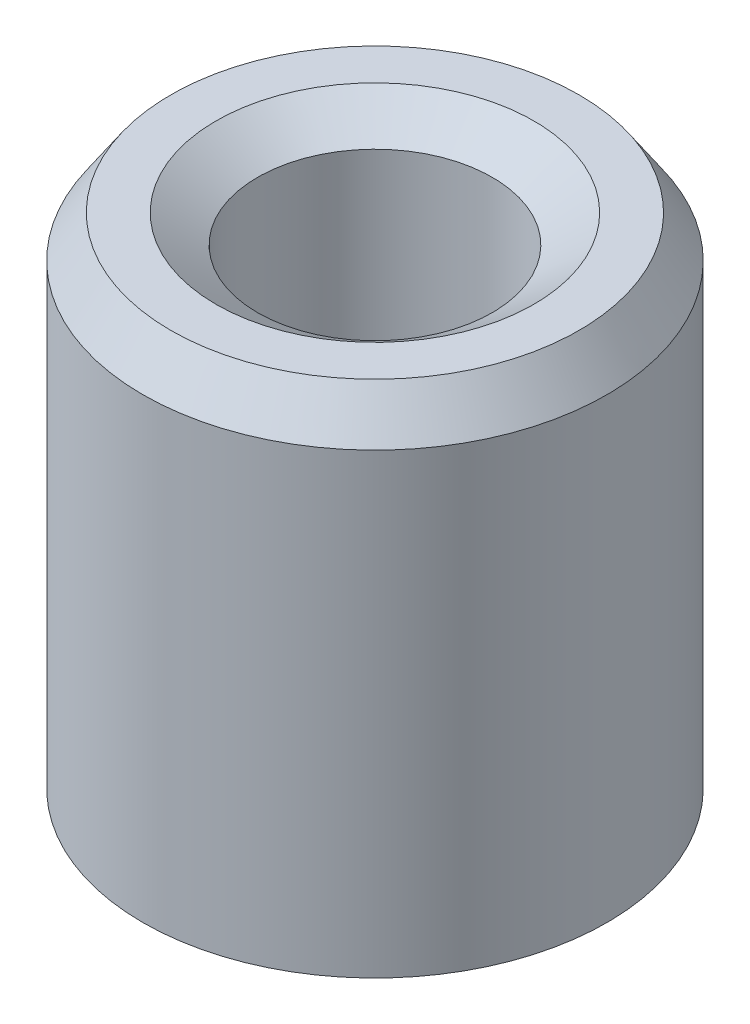
SolidWorks part; units mm, degrees
ref_plane "Front Plane" through (0, 0, 0) normal (0, 0, 1) x (1, 0, 0)
ref_plane "Top Plane" through (0, 0, 0) normal (0, 1, 0) x (1, 0, 0)
ref_plane "Right Plane" through (0, 0, 0) normal (1, 0, 0) x (0, 0, -1)
sketch "Sketch1" plane through (0, 0, 0) normal (0, 1, 0) x (1, 0, 0)
  circle A0 centre (0, 0) radius 5
  dimension "SLEEVE_OD" = 10
extrude "Boss-Extrude1" add sketch "Sketch1" along normal blind 11.3471
sketch "Sketch2" plane through (0, 0, 0) normal (0, 1, 0) x (1, 0, 0)
  circle A0 centre (0, 0) radius 2.527
  dimension "BORE_D" = 5.0541
extrude "Cut-Extrude1" cut sketch "Sketch2" along normal through all
chamfer "Chamfer1" distance 0.8961 angle 33.966 4 edges at (0, 11.3471, 2.527) (0, 0, 2.527) (0, 0, 5) (0, 11.3471, 5) first distance on face at (0, 11.3471, 2.527) first distance on face at (0, 0, 2.527) first distance on face at (0, 11.3471, 5)
